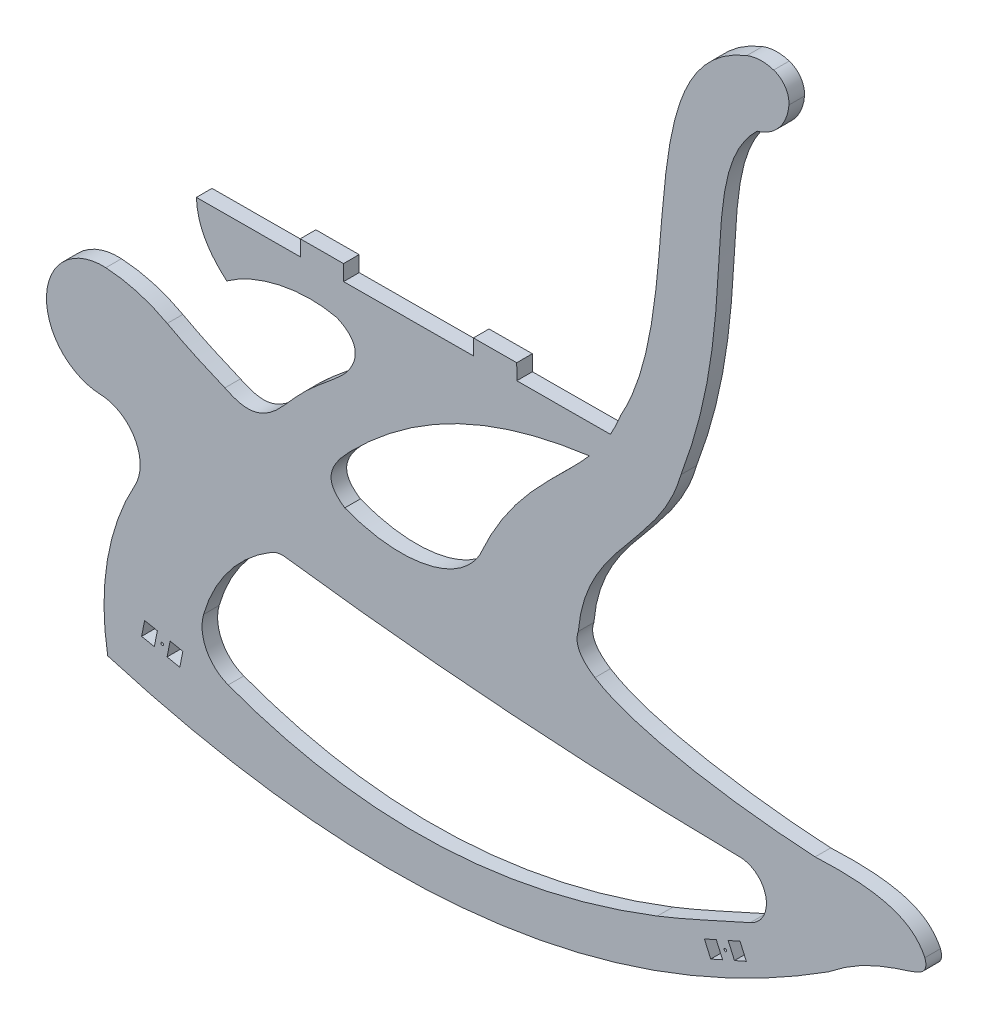
SolidWorks part; units mm, degrees
material "Teak"
ref_plane "Front Plane" through (0, 0, 0) normal (0, 0, 1) x (1, 0, 0)
ref_plane "Top Plane" through (0, 0, 0) normal (0, 1, 0) x (1, 0, 0)
ref_plane "Right Plane" through (0, 0, 0) normal (1, 0, 0) x (0, 0, -1)
sketch "Несущая боковая" plane through (0, 0, 0) normal (0, 0, 1) x (1, 0, 0)
  line L6 (398.785, -200.6515) -> (-79.2948, -202.7)
  arc A0 (568.0858, 187.1743) -> (604.9253, 231.748) centre (555.0835, 235.431) ccw
  arc A1 (604.9253, 231.748) -> (587.3016, 257.9076) centre (579.4885, 233.6276) ccw
  arc A2 (587.3016, 257.9076) -> (556.344, 256.9224) centre (573.2016, 214.0906) ccw
  arc A4 (-150.2921, -526.2545) -> (-190.0816, -455.2016) centre (-192.0175, -502.9531) ccw
  arc A7 (-150.2921, -526.2545) -> (-181.6944, -712.4375) centre (95.3308, -663.4217) ccw
  arc A8 (-183.8786, -325.353) -> (-190.0816, -455.2016) centre (-187.4487, -390.2549) ccw
  arc A9 (-112.9747, -345.6094) -> (-183.8786, -325.353) centre (-193.0224, -491.581) ccw
  arc A10 (560.3467, -608.2215) -> (548.1989, -548.57) centre (547.8281, -579.7082) ccw
  arc A11 (23.5507, -511.1423) -> (548.1989, -548.57) centre (601.0308, 3887.8918) ccw
  arc A12 (7.2112, -514.4863) -> (-70.9864, -615.6156) centre (95.3308, -663.4217) ccw
  arc A13 (-70.9864, -615.6156) -> (-42.6063, -671.9817) centre (-26.3207, -628.4543) ccw
  arc A14 (23.5507, -511.1423) -> (7.2112, -514.4863) centre (20.2245, -536.4807) ccw
  spline S0 degree 3 poles (556.344, 256.9224) (413.4931, 200.7) (492.8039, -30.4464) (410.7267, -175.5993) knots 0.000401 0.000401 0.000401 0.000401 0.043478 0.043478 0.043478 0.043478
  spline S1 degree 3 poles (410.7267, -175.5993) (407.231, -184.6492) (403.2193, -192.9282) (398.785, -200.6515) knots 0.043478 0.043478 0.043478 0.043478 0.086957 0.086957 0.086957 0.086957
  spline S2 degree 3 poles (-79.2948, -202.7) (-78.5172, -227.7) (-66.7741, -249.7094) (-44.1772, -268.7587) knots 0.130435 0.130435 0.130435 0.130435 0.173913 0.173913 0.173913 0.173913
  spline S3 degree 3 poles (-44.1772, -268.7587) (-12.7058, -245.829) (38.9597, -231.7344) (82.6666, -241.804) knots 0.173913 0.173913 0.173913 0.173913 0.217391 0.217391 0.217391 0.217391
  spline S4 degree 3 poles (82.6666, -241.804) (105.6787, -251.6525) (111.2464, -268.6919) (94.2115, -290.7234) knots 0.217391 0.217391 0.217391 0.217391 0.26087 0.26087 0.26087 0.26087
  spline S5 degree 3 poles (94.2115, -290.7234) (87.1581, -299.8457) (74.9831, -308.4217) (61.0599, -320.5021) knots 0.26087 0.26087 0.26087 0.26087 0.304348 0.304348 0.304348 0.304348
  spline S6 degree 3 poles (61.0599, -320.5021) (47.3806, -331.8412) (34.8832, -345.2678) (22.8705, -359.1067) knots 0.304348 0.304348 0.304348 0.304348 0.347826 0.347826 0.347826 0.347826
  spline S7 degree 3 poles (22.8705, -359.1067) (-5.5844, -391.8897) (-25.5922, -386.6363) (-46.4172, -376.7876) knots 0.347826 0.347826 0.347826 0.347826 0.391304 0.391304 0.391304 0.391304
  spline S8 degree 3 poles (-46.4172, -376.7876) (-71.9902, -366.2219) (-92.784, -356.6815) (-112.9747, -345.6094) knots 0.391304 0.391304 0.391304 0.391304 0.434783 0.434783 0.434783 0.434783
  spline S14 degree 3 poles (-181.6944, -712.4375) (138.4622, -807.7317) (410.6911, -765.399) (650.1904, -612.5982) knots 0.652174 0.652174 0.652174 0.652174 0.695652 0.695652 0.695652 0.695652
  spline S15 degree 3 poles (650.1904, -612.5982) (721.7263, -555.1366) (771.3742, -572.8028) (761.971, -542.4383) knots 0.695652 0.695652 0.695652 0.695652 0.73913 0.73913 0.73913 0.73913
  spline S16 degree 3 poles (761.971, -542.4383) (749.9881, -518.2511) (723.1034, -500.8362) (635.2399, -505.0064) knots 0.73913 0.73913 0.73913 0.73913 0.782609 0.782609 0.782609 0.782609
  spline S17 degree 3 poles (635.2399, -505.0064) (572.992, -501.9328) (433.5503, -486.7788) (380.9104, -452.9037) knots 0.782609 0.782609 0.782609 0.782609 0.826087 0.826087 0.826087 0.826087
  spline S18 degree 3 poles (380.9104, -452.9037) (364.7659, -442.5143) (356.7862, -430.3638) (361.7026, -416.2609) knots 0.826087 0.826087 0.826087 0.826087 0.869565 0.869565 0.869565 0.869565
  spline S19 degree 3 poles (361.7026, -416.2609) (369.7577, -319.5618) (455.7474, -287.137) (480.2427, -200.3025) knots 0.869565 0.869565 0.869565 0.869565 0.913043 0.913043 0.913043 0.913043
  spline S20 degree 3 poles (480.2427, -200.3025) (553.5443, -5.6015) (495.01, 115.2768) (568.0858, 187.1743) knots 0.913043 0.913043 0.913043 0.913043 0.956522 0.956522 0.956522 0.956522
  spline S25 degree 3 poles (452.9574, -655.3702) (274.7112, -724.495) (109.7393, -728.981) (-42.6063, -671.9817) knots 0.555556 0.555556 0.555556 0.555556 0.666667 0.666667 0.666667 0.666667
  spline S26 degree 3 poles (560.3467, -608.2215) (524.5503, -623.9377) (490.7002, -640.4881) (452.9574, -655.3702) knots 0.444444 0.444444 0.444444 0.444444 0.555556 0.555556 0.555556 0.555556
  spline S31 degree 3 poles (97.4618, -368.9486) (168.6207, -296.3511) (255.442, -250.0892) (374.5085, -234.3308) knots 0.75 0.75 0.75 0.75 1 1 1 1
  spline S32 degree 3 poles (92.0908, -427.5464) (69.7947, -412.5311) (70.4905, -396.4567) (97.4618, -368.9486) knots 0.5 0.5 0.5 0.5 0.75 0.75 0.75 0.75
  spline S33 degree 3 poles (247.8827, -396.6458) (222.4754, -441.0979) (152.6914, -451.7196) (92.0908, -427.5464) knots 0.25 0.25 0.25 0.25 0.5 0.5 0.5 0.5
  spline S34 degree 3 poles (374.5085, -234.3308) (336.7044, -278.0035) (285.6362, -310.9643) (247.8827, -396.6458) knots 0 0 0 0 0.25 0.25 0.25 0.25
  dimension "D2" = 65
sketch "Боковая под поперечины" plane through (0, 0, 0) normal (0, 0, 1) x (1, 0, 0)
  line L15 (-159.6049, -346.9107) -> (-207.6507, -344.8161) construction
  line L16 (-207.6507, -344.8161) -> (-235.0021, -434.5683)
  line L56 (-207.6507, -344.8161) -> (-159.6963, -346.9068)
  line L57 (-159.6963, -346.9068) -> (-148.2015, -350.3521)
  line L58 (-148.2015, -350.3521) -> (-104.2437, -369.6319)
  line L59 (-104.2437, -369.6319) -> (-95.353, -374.2095)
  line L60 (-95.353, -374.2095) -> (-51.5894, -393.9261)
  line L61 (-51.5894, -393.9261) -> (-42.3459, -397.7417)
  line L62 (-42.3459, -397.7417) -> (2.1537, -415.7357)
  line L63 (2.1537, -415.7357) -> (11.4455, -419.432)
  line L64 (11.4455, -419.432) -> (56.3986, -436.2612)
  line L65 (56.3986, -436.2612) -> (65.8381, -439.5619)
  line L66 (65.8381, -439.5619) -> (111.7403, -453.5971)
  line L67 (111.7403, -453.5971) -> (121.3499, -456.3643)
  line L68 (121.3499, -456.3643) -> (169.2689, -459.1514)
  line L69 (169.2689, -459.1514) -> (179.2066, -458.0374)
  line L70 (179.2066, -458.0374) -> (224.5179, -442.198)
  line L71 (224.5179, -442.198) -> (232.8956, -436.7378)
  line L72 (232.8956, -436.7378) -> (261.7321, -398.3651)
  line L73 (261.7321, -398.3651) -> (267.2053, -389.9959)
  line L74 (267.2053, -389.9959) -> (294.9373, -350.8177)
  line L75 (294.9373, -350.8177) -> (300.8954, -342.7864)
  line L76 (300.8954, -342.7864) -> (330.585, -305.0699)
  line L77 (330.585, -305.0699) -> (336.9867, -297.3877)
  line L78 (336.9867, -297.3877) -> (368.9263, -261.5566)
  line L79 (368.9263, -261.5566) -> (376.1332, -254.6241)
  line L80 (376.1332, -254.6241) -> (406.9239, -217.801)
  line L81 (406.9239, -217.801) -> (412.4436, -209.4624)
  line L82 (412.4436, -209.4624) -> (434.4129, -166.7851)
  line L83 (438.0837, -157.4832) -> (452.6073, -111.7332)
  line L84 (452.6073, -111.7332) -> (454.9033, -102.0003)
  line L85 (454.9033, -102.0003) -> (464.25, -54.9191)
  line L86 (464.25, -54.9191) -> (465.6878, -45.023)
  line L87 (465.6878, -45.023) -> (472.014, 2.5582)
  line L88 (472.014, 2.5582) -> (473.0512, 12.5043)
  line L89 (473.0512, 12.5043) -> (478.3742, 60.2082)
  line L90 (478.3742, 60.2082) -> (479.4656, 70.1485)
  line L91 (479.4656, 70.1485) -> (486.2184, 117.6711)
  line L92 (486.2184, 117.6711) -> (487.9962, 127.5118)
  line L93 (487.9962, 127.5118) -> (500.2801, 173.9134)
  line L94 (500.2801, 173.9134) -> (504.8877, 188.1882)
  line L95 (504.8877, 188.1882) -> (532.6089, 227.3741)
  line L96 (532.6089, 227.3741) -> (546.1164, 235.9502)
  line L97 (546.1164, 235.9502) -> (589.1375, 257.2382)
  line L99 (434.4129, -166.7851) -> (438.0837, -157.4832)
  arc A4 (568.0858, 187.1743) -> (604.9253, 231.748) centre (554.9668, 235.5274) ccw
  arc A7 (604.9253, 231.748) -> (589.1375, 257.2382) centre (579.4223, 233.5866) ccw
  arc A10 (604.9253, 231.748) -> (587.3016, 257.9076) centre (579.4885, 233.6276) ccw construction
  arc A11 (-144.8294, -495.3868) -> (-22.9392, -537.0926) centre (-72.7974, -483.8369) ccw
  arc A12 (7.2112, -514.4863) -> (-22.9392, -537.0926) centre (95.3308, -663.4217) ccw
  arc A13 (23.5507, -511.1423) -> (7.2112, -514.4863) centre (20.2245, -536.4807) ccw
  arc A15 (-144.8294, -495.3868) -> (-190.0816, -455.2016) centre (-192.0175, -502.9531) ccw
  arc A16 (23.5507, -511.1423) -> (352.014, -541.8909) centre (601.0308, 3887.8918) ccw
  arc A17 (-150.2921, -526.2545) -> (-190.0816, -455.2016) centre (-192.0175, -502.9531) ccw construction
  arc A18 (-183.8786, -325.353) -> (-190.0816, -455.2016) centre (-187.4487, -390.2549) ccw construction
  arc A19 (-235.0021, -434.5683) -> (-190.0816, -455.2016) centre (-187.4487, -390.2549) ccw
  arc A20 (23.5507, -511.1423) -> (548.1989, -548.57) centre (601.0308, 3887.8918) ccw construction
  arc A21 (23.5507, -511.1423) -> (7.2112, -514.4863) centre (20.2245, -536.4807) ccw construction
  arc A22 (7.2112, -514.4863) -> (-70.9864, -615.6156) centre (95.3308, -663.4217) ccw construction
  arc A23 (352.014, -541.8909) -> (380.9104, -452.9037) centre (354.7294, -493.5874) ccw
  spline S13 degree 3 poles (380.9104, -452.9037) (364.7659, -442.5143) (356.7861, -430.3638) (361.7026, -416.2609) knots 0.5 0.5 0.5 0.5 0.533333 0.533333 0.533333 0.533333
  spline S14 degree 3 poles (361.7026, -416.2609) (369.7577, -319.5618) (455.7474, -287.137) (480.2427, -200.3025) knots 0.533333 0.533333 0.533333 0.533333 0.566667 0.566667 0.566667 0.566667
  spline S15 degree 3 poles (480.2427, -200.3025) (553.5444, -5.6014) (495.0101, 115.2768) (568.0858, 187.1743) knots 0.566667 0.566667 0.566667 0.566667 0.6 0.6 0.6 0.6
  point P66 (608.2751, 264.1653)
  point P67 (553.7309, 240.2756)
  point P74 (-221.3236, -344.22)
  dimension "D1" = 48
  dimension "D2" = 12
  dimension "D3" = 10
  dimension "D10" = 16
  dimension "D11" = 15
extrude "Несущая" add sketch "Несущая боковая" along normal blind 18
extrude "Боковая" [suppressed] add sketch "Боковая под поперечины" along normal blind 18
sketch "Sketch3" [suppressed] plane through (0, 0, 0) normal (0, 0, 1) x (1, 0, 0)
  line L0 (546.1164, 235.9502) -> (589.1375, 257.2382) construction
  line L2 (-212.8786, -423.719) -> (-206.4654, -402.6745)
  line L3 (-230.0968, -418.4719) -> (-223.6836, -397.4273)
  line L6 (-230.0968, -418.4719) -> (-212.8786, -423.719)
  line L10 (-207.6507, -344.8161) -> (-194.6631, -345.3823) construction
  line L11 (-207.6507, -344.8161) -> (-208.4348, -362.799) construction
  line L12 (-159.6963, -346.9068) -> (-160.4803, -364.8897) construction
  line L13 (-208.4348, -362.799) -> (-195.4471, -363.3652) construction
  line L14 (-194.6631, -345.3823) -> (-195.4471, -363.3652)
  line L15 (-172.684, -346.3405) -> (-173.468, -364.3234)
  line L16 (-173.468, -364.3234) -> (-160.4803, -364.8897) construction
  line L17 (-195.4471, -363.3652) -> (-173.468, -364.3234)
  line L18 (-172.684, -346.3405) -> (-159.6963, -346.9068) construction
  line L19 (-194.6631, -345.3823) -> (-172.684, -346.3405)
  line L37 (-136.2963, -355.5737) -> (-143.5262, -372.0579)
  line L38 (-116.149, -364.4103) -> (-123.3789, -380.8944)
  line L40 (-155.4315, -366.8363) -> (-143.5262, -372.0579) construction
  line L41 (-116.149, -364.4103) -> (-104.2437, -369.6319) construction
  line L42 (-143.5262, -372.0579) -> (-123.3789, -380.8944)
  line L43 (-104.2437, -369.6319) -> (-111.4736, -386.1161) construction
  line L44 (-123.3789, -380.8944) -> (-111.4736, -386.1161) construction
  line L45 (-148.2015, -350.3521) -> (-136.2963, -355.5737) construction
  line L46 (-136.2963, -355.5737) -> (-116.149, -364.4103)
  line L47 (-148.2015, -350.3521) -> (-155.4315, -366.8363) construction
  line L48 (-104.2437, -369.6319) -> (-148.2015, -350.3521) construction
  line L49 (-63.442, -388.5862) -> (-70.8357, -404.9976)
  line L50 (-83.5003, -379.5494) -> (-63.442, -388.5862)
  line L51 (-83.5003, -379.5494) -> (-90.8941, -395.9608)
  line L52 (-63.442, -388.5862) -> (-51.5894, -393.9261) construction
  line L53 (-102.7467, -390.6208) -> (-90.8941, -395.9608) construction
  line L54 (-51.5894, -393.9261) -> (-58.9831, -410.3375) construction
  line L55 (-95.353, -374.2095) -> (-83.5003, -379.5494) construction
  line L56 (-90.8941, -395.9608) -> (-70.8357, -404.9976)
  line L57 (-70.8357, -404.9976) -> (-58.9831, -410.3375) construction
  line L58 (-95.353, -374.2095) -> (-102.7467, -390.6208) construction
  line L59 (-37.0417, -419.3024) -> (-16.646, -427.5497)
  line L60 (-30.2939, -402.615) -> (-9.8983, -410.8623)
  line L61 (-42.3459, -397.7417) -> (-30.2939, -402.615) construction
  line L62 (-9.8983, -410.8623) -> (2.1537, -415.7357) construction
  line L63 (-49.0936, -414.429) -> (-37.0417, -419.3024) construction
  line L64 (-9.8983, -410.8623) -> (-16.646, -427.5497)
  line L65 (-42.3459, -397.7417) -> (-49.0936, -414.429) construction
  line L66 (-16.646, -427.5497) -> (-4.594, -432.423) construction
  line L67 (-30.2939, -402.615) -> (-37.0417, -419.3024)
  line L68 (2.1537, -415.7357) -> (-4.594, -432.423) construction
  line L69 (44.2238, -431.7033) -> (37.9128, -448.5607)
  line L70 (56.3986, -436.2612) -> (50.0876, -453.1186) construction
  line L71 (23.6203, -423.9899) -> (44.2238, -431.7033)
  line L72 (23.6203, -423.9899) -> (17.3094, -440.8473)
  line L73 (5.1346, -436.2894) -> (17.3094, -440.8473) construction
  line L74 (11.4455, -419.432) -> (23.6203, -423.9899) construction
  line L75 (44.2238, -431.7033) -> (56.3986, -436.2612) construction
  line L76 (11.4455, -419.432) -> (5.1346, -436.2894) construction
  line L77 (37.9128, -448.5607) -> (50.0876, -453.1186) construction
  line L78 (17.3094, -440.8473) -> (37.9128, -448.5607)
  line L79 (94.0453, -467.0093) -> (106.4771, -470.8105) construction
  line L80 (65.8381, -439.5619) -> (60.5749, -456.7753) construction
  line L81 (99.3085, -449.7959) -> (94.0453, -467.0093)
  line L82 (78.27, -443.3631) -> (73.0068, -460.5765)
  line L83 (65.8381, -439.5619) -> (78.27, -443.3631) construction
  line L84 (60.5749, -456.7753) -> (73.0068, -460.5765) construction
  line L85 (99.3085, -449.7959) -> (111.7403, -453.5971) construction
  line L86 (111.7403, -453.5971) -> (106.4771, -470.8105) construction
  line L87 (73.0068, -460.5765) -> (94.0453, -467.0093)
  line L88 (78.27, -443.3631) -> (99.3085, -449.7959)
  line L89 (120.3047, -474.3339) -> (133.2828, -475.0888) construction
  line L90 (156.2908, -458.3965) -> (169.2689, -459.1514) construction
  line L91 (133.2828, -475.0888) -> (155.2457, -476.3662)
  line L92 (156.2908, -458.3965) -> (155.2457, -476.3662)
  line L93 (155.2457, -476.3662) -> (168.2237, -477.121) construction
  line L94 (121.3499, -456.3643) -> (134.3279, -457.1191) construction
  line L95 (134.3279, -457.1191) -> (156.2908, -458.3965)
  line L96 (121.3499, -456.3643) -> (120.3047, -474.3339) construction
  line L97 (134.3279, -457.1191) -> (133.2828, -475.0888)
  line L98 (169.2689, -459.1514) -> (168.2237, -477.121) construction
  line L99 (218.1859, -463.4795) -> (230.4577, -459.1897) construction
  line L100 (191.4784, -453.7475) -> (212.2461, -446.4878)
  line L101 (191.4784, -453.7475) -> (197.4182, -470.7393)
  line L102 (185.1464, -475.0291) -> (197.4182, -470.7393) construction
  line L103 (224.5179, -442.198) -> (230.4577, -459.1897) construction
  line L104 (197.4182, -470.7393) -> (218.1859, -463.4795)
  line L105 (179.2066, -458.0374) -> (185.1464, -475.0291) construction
  line L106 (212.2461, -446.4878) -> (224.5179, -442.198) construction
  line L107 (179.2066, -458.0374) -> (191.4784, -453.7475) construction
  line L108 (212.2461, -446.4878) -> (218.1859, -463.4795)
  line L109 (255.0952, -437.1589) -> (268.312, -419.5714)
  line L110 (268.312, -419.5714) -> (276.1219, -409.1788) construction
  line L111 (247.2854, -447.5514) -> (255.0952, -437.1589) construction
  line L112 (240.7055, -426.3452) -> (255.0952, -437.1589)
  line L113 (253.9222, -408.7577) -> (261.7321, -398.3651) construction
  line L114 (261.7321, -398.3651) -> (276.1219, -409.1788) construction
  line L115 (232.8956, -436.7378) -> (240.7055, -426.3452) construction
  line L116 (240.7055, -426.3452) -> (253.9222, -408.7577)
  line L117 (232.8956, -436.7378) -> (247.2854, -447.5514) construction
  line L118 (253.9222, -408.7577) -> (268.312, -419.5714)
  line L119 (267.2053, -389.9959) -> (274.7161, -379.3851) construction
  line L120 (267.2053, -389.9959) -> (281.8971, -400.3954) construction
  line L121 (281.8971, -400.3954) -> (289.4079, -389.7846) construction
  line L122 (274.7161, -379.3851) -> (289.4079, -389.7846)
  line L123 (289.4079, -389.7846) -> (302.1184, -371.828)
  line L124 (287.4266, -361.4284) -> (302.1184, -371.828)
  line L125 (294.9373, -350.8177) -> (309.6292, -361.2172) construction
  line L126 (302.1184, -371.828) -> (309.6292, -361.2172) construction
  line L127 (287.4266, -361.4284) -> (294.9373, -350.8177) construction
  line L128 (274.7161, -379.3851) -> (287.4266, -361.4284)
  line L129 (336.6877, -326.4184) -> (344.7286, -316.2035) construction
  line L130 (323.08, -343.7051) -> (336.6877, -326.4184)
  line L131 (308.9363, -332.5715) -> (322.5441, -315.2848)
  line L132 (300.8954, -342.7864) -> (308.9363, -332.5715) construction
  line L133 (300.8954, -342.7864) -> (315.0391, -353.92) construction
  line L134 (308.9363, -332.5715) -> (323.08, -343.7051)
  line L135 (322.5441, -315.2848) -> (336.6877, -326.4184)
  line L136 (315.0391, -353.92) -> (323.08, -343.7051) construction
  line L137 (330.585, -305.0699) -> (344.7286, -316.2035) construction
  line L138 (322.5441, -315.2848) -> (330.585, -305.0699) construction
  line L139 (336.9867, -297.3877) -> (350.4234, -309.365) construction
  line L140 (360.276, -271.2609) -> (373.7127, -283.2382)
  line L141 (373.7127, -283.2382) -> (382.363, -273.534) construction
  line L142 (350.4234, -309.365) -> (359.0737, -299.6608) construction
  line L143 (359.0737, -299.6608) -> (373.7127, -283.2382)
  line L144 (336.9867, -297.3877) -> (345.637, -287.6834) construction
  line L145 (368.9263, -261.5566) -> (382.363, -273.534) construction
  line L146 (360.276, -271.2609) -> (368.9263, -261.5566) construction
  line L147 (345.637, -287.6834) -> (360.276, -271.2609)
  line L148 (345.637, -287.6834) -> (359.0737, -299.6608)
  line L149 (412.3934, -239.3204) -> (420.7325, -229.3475) construction
  line L150 (398.5847, -227.7739) -> (412.3934, -239.3204)
  line L151 (398.281, -256.1976) -> (412.3934, -239.3204)
  line L152 (389.9419, -266.1706) -> (398.281, -256.1976) construction
  line L153 (406.9239, -217.801) -> (420.7325, -229.3475) construction
  line L154 (376.1332, -254.6241) -> (384.4724, -244.6512) construction
  line L155 (376.1332, -254.6241) -> (389.9419, -266.1706) construction
  line L156 (398.5847, -227.7739) -> (406.9239, -217.801) construction
  line L157 (384.4724, -244.6512) -> (398.281, -256.1976)
  line L158 (384.4724, -244.6512) -> (398.5847, -227.7739)
  line L159 (444.4669, -186.5821) -> (450.4169, -175.0237) construction
  line L160 (428.4629, -178.3436) -> (434.4129, -166.7851) construction
  line L161 (428.4629, -178.3436) -> (444.4669, -186.5821)
  line L162 (418.3936, -197.904) -> (434.3976, -206.1425)
  line L163 (434.3976, -206.1425) -> (444.4669, -186.5821)
  line L164 (412.4436, -209.4624) -> (428.4475, -217.7009) construction
  line L165 (428.4475, -217.7009) -> (434.3976, -206.1425) construction
  line L166 (434.4129, -166.7851) -> (450.4169, -175.0237) construction
  line L167 (418.3936, -197.904) -> (428.4629, -178.3436)
  line L168 (412.4436, -209.4624) -> (418.3936, -197.904) construction
  line L169 (455.24, -162.9296) -> (459.1734, -150.5389) construction
  line L170 (448.6738, -124.1238) -> (452.6073, -111.7332) construction
  line L171 (442.0172, -145.0926) -> (459.1734, -150.5389)
  line L172 (448.6738, -124.1238) -> (465.8301, -129.5702)
  line L173 (438.0837, -157.4832) -> (442.0172, -145.0926) construction
  line L174 (465.8301, -129.5702) -> (469.7635, -117.1795) construction
  line L175 (442.0172, -145.0926) -> (448.6738, -124.1238)
  line L176 (452.6073, -111.7332) -> (469.7635, -117.1795) construction
  line L177 (438.0837, -157.4832) -> (455.24, -162.9296) construction
  line L178 (459.1734, -150.5389) -> (465.8301, -129.5702)
  line L179 (-51.5894, -393.9261) -> (-95.353, -374.2095) construction
  line L180 (2.1537, -415.7357) -> (-42.3459, -397.7417) construction
  line L181 (56.3986, -436.2612) -> (11.4455, -419.432) construction
  line L182 (368.9263, -261.5566) -> (336.9867, -297.3877) construction
  line L183 (406.9239, -217.801) -> (376.1332, -254.6241) construction
  line L184 (434.4129, -166.7851) -> (412.4436, -209.4624) construction
  line L185 (452.6073, -111.7332) -> (438.0837, -157.4832) construction
  line L186 (472.5587, -105.5054) -> (475.0901, -92.7542) construction
  line L187 (457.4347, -89.2492) -> (461.7186, -67.6703)
  line L188 (454.9033, -102.0003) -> (457.4347, -89.2492) construction
  line L189 (457.4347, -89.2492) -> (475.0901, -92.7542)
  line L190 (461.7186, -67.6703) -> (464.25, -54.9191) construction
  line L191 (454.9033, -102.0003) -> (472.5587, -105.5054) construction
  line L192 (464.25, -54.9191) -> (481.9054, -58.4242) construction
  line L193 (475.0901, -92.7542) -> (479.374, -71.1753)
  line L194 (461.7186, -67.6703) -> (479.374, -71.1753)
  line L195 (479.374, -71.1753) -> (481.9054, -58.4242) construction
  line L196 (467.4011, -32.1364) -> (470.3006, -10.3284)
  line L197 (465.6878, -45.023) -> (467.4011, -32.1364) construction
  line L198 (472.014, 2.5582) -> (489.857, 0.1859) construction
  line L199 (485.2441, -34.5088) -> (488.1436, -12.7007)
  line L200 (470.3006, -10.3284) -> (472.014, 2.5582) construction
  line L201 (488.1436, -12.7007) -> (489.857, 0.1859) construction
  line L202 (465.6878, -45.023) -> (483.5308, -47.3954) construction
  line L203 (467.4011, -32.1364) -> (485.2441, -34.5088)
  line L204 (470.3006, -10.3284) -> (488.1436, -12.7007)
  line L205 (483.5308, -47.3954) -> (485.2441, -34.5088) construction
  line L206 (473.0512, 12.5043) -> (474.4928, 25.4241) construction
  line L207 (474.4928, 25.4241) -> (476.9325, 47.2884)
  line L208 (473.0512, 12.5043) -> (490.9401, 10.5082) construction
  line L209 (494.8215, 45.2923) -> (496.2632, 58.2121) construction
  line L210 (476.9325, 47.2884) -> (494.8215, 45.2923)
  line L211 (474.4928, 25.4241) -> (492.3818, 23.428)
  line L212 (490.9401, 10.5082) -> (492.3818, 23.428) construction
  line L213 (492.3818, 23.428) -> (494.8215, 45.2923)
  line L214 (478.3742, 60.2082) -> (496.2632, 58.2121) construction
  line L215 (476.9325, 47.2884) -> (478.3742, 60.2082) construction
  line L216 (486.2184, 117.6711) -> (504.0394, 115.1388) construction
  line L217 (481.2945, 83.0192) -> (484.3895, 104.8004)
  line L218 (499.1154, 80.4869) -> (502.2105, 102.2681)
  line L219 (502.2105, 102.2681) -> (504.0394, 115.1388) construction
  line L220 (484.3895, 104.8004) -> (486.2184, 117.6711) construction
  line L221 (484.3895, 104.8004) -> (502.2105, 102.2681)
  line L222 (479.4656, 70.1485) -> (481.2945, 83.0192) construction
  line L223 (479.4656, 70.1485) -> (497.2865, 67.6162) construction
  line L224 (481.2945, 83.0192) -> (499.1154, 80.4869)
  line L225 (497.2865, 67.6162) -> (499.1154, 80.4869) construction
  line L226 (500.2801, 173.9134) -> (517.6807, 169.307) construction
  line L227 (505.3968, 122.9054) -> (508.7237, 135.4725) construction
  line L228 (491.3231, 140.0789) -> (496.9532, 161.3463)
  line L229 (514.3538, 156.7399) -> (517.6807, 169.307) construction
  line L230 (487.9962, 127.5118) -> (491.3231, 140.0789) construction
  line L231 (487.9962, 127.5118) -> (505.3968, 122.9054) construction
  line L232 (491.3231, 140.0789) -> (508.7237, 135.4725)
  line L233 (496.9532, 161.3463) -> (514.3538, 156.7399)
  line L234 (508.7237, 135.4725) -> (514.3538, 156.7399)
  line L235 (496.9532, 161.3463) -> (500.2801, 173.9134) construction
  line L236 (512.3955, 198.8011) -> (525.1011, 216.7613)
  line L237 (504.8877, 188.1882) -> (519.5824, 177.7928) construction
  line L238 (525.1011, 216.7613) -> (532.6089, 227.3741) construction
  line L239 (512.3955, 198.8011) -> (527.0902, 188.4056)
  line L240 (525.1011, 216.7613) -> (539.7958, 206.3658)
  line L241 (532.6089, 227.3741) -> (547.3036, 216.9787) construction
  line L242 (504.8877, 188.1882) -> (512.3955, 198.8011) construction
  line L243 (539.7958, 206.3658) -> (547.3036, 216.9787) construction
  line L244 (519.5824, 177.7928) -> (527.0902, 188.4056) construction
  line L245 (527.0902, 188.4056) -> (539.7958, 206.3658)
  line L246 (589.1375, 257.2382) -> (597.1205, 241.1053) construction
  line L247 (557.7679, 241.7157) -> (565.7509, 225.5827)
  line L248 (546.1164, 235.9502) -> (557.7679, 241.7157) construction
  line L249 (577.4859, 251.4727) -> (585.469, 235.3398)
  line L250 (585.469, 235.3398) -> (597.1205, 241.1053) construction
  line L251 (557.7679, 241.7157) -> (577.4859, 251.4727)
  line L252 (546.1164, 235.9502) -> (554.0994, 219.8172) construction
  line L253 (565.7509, 225.5827) -> (585.469, 235.3398)
  line L254 (577.4859, 251.4727) -> (589.1375, 257.2382) construction
  line L255 (554.0994, 219.8172) -> (565.7509, 225.5827) construction
  line L256 (464.25, -54.9191) -> (454.9033, -102.0003) construction
  line L257 (472.014, 2.5582) -> (465.6878, -45.023) construction
  line L258 (486.2184, 117.6711) -> (479.4656, 70.1485) construction
  line L259 (500.2801, 173.9134) -> (487.9962, 127.5118) construction
  line L260 (487.9962, 127.5118) -> (486.2184, 117.6711) construction
  line L261 (532.6089, 227.3741) -> (504.8877, 188.1882) construction
  line L262 (504.8877, 188.1882) -> (500.2801, 173.9134) construction
  line L264 (-223.6836, -397.4273) -> (-206.4654, -402.6745)
  line L269 (-207.6507, -344.8161) -> (-235.0021, -434.5683) construction
  point P1 (-226.8902, -407.9496)
  dimension "D1" = 66
  dimension "D2" = 18
  dimension "D3" = 22
extrude "Шипы" [suppressed] cut sketch "Sketch3" along normal through all
sketch "Sketch4" [suppressed] plane through (0, 0, 18) normal (0, 0, 1) x (1, 0, 0)
  line L0 (-208.4348, -362.799) -> (-221.0097, -388.653) construction
  line L1 (-221.0097, -388.653) -> (-207.6507, -344.8161) construction
  line L2 (-207.6507, -344.8161) -> (-208.4348, -362.799) construction
  line L4 (-217.7838, -439.8154) -> (-237.4507, -429.7729) construction
  line L5 (-237.4507, -429.7729) -> (-240.164, -452.0896) construction
  line L6 (-240.164, -452.0896) -> (-213.0497, -450.0009) construction
  arc A1 (-235.0021, -434.5683) -> (-190.0816, -455.2016) centre (-187.4487, -390.2549) ccw construction
extrude "Излишки" [suppressed] cut sketch "Sketch4" against normal up to next
sketch "Sketch5" plane through (0, 0, 18) normal (0, 0, 1) x (1, 0, 0)
  line L1 (40.627, -184.186) -> (90.6265, -183.9718)
  line L2 (40.627, -184.186) -> (40.7041, -202.1858)
  line L3 (40.7041, -202.1858) -> (90.7037, -201.9716)
  line L4 (90.6265, -183.9718) -> (90.7037, -201.9716)
  line L5 (398.785, -200.6515) -> (-79.2948, -202.7) construction
  line L6 (240.6251, -183.329) -> (290.6247, -183.1148)
  line L7 (240.6251, -183.329) -> (240.7023, -201.3289)
  line L8 (240.7023, -201.3289) -> (290.7018, -201.1146)
  line L9 (290.6247, -183.1148) -> (290.7018, -201.1146)
  dimension "D1" = 18
  dimension "D2" = 150
  dimension "D3" = 120
  dimension "D4" = 50
extrude "Шипы на подлокотниках" add sketch "Sketch5" against normal up to surface (18 mm away) up to face at (168.5307, -593.8353, 0)
sketch "Sketch6" plane through (0, 0, 18) normal (0, 0, 1) x (1, 0, 0)
  line L0 (-139.0626, -655.7461) -> (-142.5889, -673.3973)
  line L1 (-142.5889, -673.3973) -> (-127.8796, -676.3359)
  line L2 (-127.8796, -676.3359) -> (-124.3533, -658.6847)
  line L3 (-124.3533, -658.6847) -> (-139.0626, -655.7461)
  line L4 (-127.8796, -676.3359) -> (-113.1702, -679.2745) construction
  line L5 (-113.1702, -679.2745) -> (-109.6439, -661.6232)
  line L6 (-109.6439, -661.6232) -> (-94.9346, -664.5618)
  line L7 (-94.9346, -664.5618) -> (-98.4609, -682.213)
  line L8 (-98.4609, -682.213) -> (-113.1702, -679.2745)
  line L9 (-120.5249, -677.8052) -> (-116.9986, -660.154) construction
  line L10 (-124.3533, -658.6847) -> (-109.6439, -661.6232) construction
  line L11 (-126.1164, -667.5103) -> (-111.4071, -670.4489) construction
  line L12 (521.0426, -644.9347) -> (534.7498, -638.8426) construction
  line L13 (555.7675, -649.1991) -> (542.0603, -655.2912)
  line L14 (535.2067, -658.3373) -> (527.8962, -641.8886) construction
  line L15 (521.0426, -644.9347) -> (507.3355, -651.0268)
  line L16 (514.646, -667.4754) -> (528.3531, -661.3833)
  line L17 (528.3531, -661.3833) -> (542.0603, -655.2912) construction
  line L18 (528.3531, -661.3833) -> (521.0426, -644.9347)
  line L19 (542.0603, -655.2912) -> (534.7498, -638.8426)
  line L20 (524.6979, -653.159) -> (538.4051, -647.0669) construction
  line L21 (548.457, -632.7505) -> (555.7675, -649.1991)
  line L22 (507.3355, -651.0268) -> (514.646, -667.4754)
  line L23 (534.7498, -638.8426) -> (548.457, -632.7505)
  circle A2 centre (531.5515, -650.113) radius 1.5
  circle A4 centre (-118.7618, -668.9796) radius 1.5
  dimension "D1" = 18
  dimension "D4" = 3
  dimension "D6" = 3
  dimension "D2" = 15
  dimension "D5" = 15
extrude "Под ребра жесткости" cut sketch "Sketch6" against normal up to next
sketch "Sketch7" [suppressed] plane through (0, 0, 18) normal (0, 0, 1) x (1, 0, 0)
  line L0 (567.6269, 246.5942) -> (583.0969, 215.468) construction
  line L1 (577.4859, 251.4727) -> (557.7679, 241.7157) construction
  circle A0 centre (583.0969, 215.468) radius 10 construction
  circle A1 centre (583.0969, 215.468) radius 4
  circle A2 centre (354.7294, -493.5874) radius 4
  circle A3 centre (-72.7974, -483.8369) radius 4
  arc A4 (352.014, -541.8909) -> (380.9104, -452.9037) centre (354.7294, -493.5874) ccw construction
  arc A5 (-144.8294, -495.3868) -> (-22.9392, -537.0926) centre (-72.7974, -483.8369) ccw construction
  dimension "D1" = 8
  dimension "D2" = 20
extrude "Под болты М8" [suppressed] cut sketch "Sketch7" against normal blind 20
sketch "Sketch9" [suppressed] plane through (0, 0, 18) normal (0, 0, 1) x (1, 0, 0)
  circle A1 centre (-150.0179, -416.742) radius 1.5
  circle A2 centre (-19.0866, -469.5934) radius 1.5
  circle A3 centre (116.1327, -506.7832) radius 1.5
  circle A4 centre (265.4187, -506.7832) radius 1.5
  circle A5 centre (335.948, -380.5609) radius 1.5
  circle A6 centre (431.4673, -250.6533) radius 1.5
  circle A7 centre (486.9514, -124.9981) radius 1.5
  circle A8 centre (512.1042, 60.8892) radius 1.5
  dimension "D1" = 3
extrude "Под шурупы" [suppressed] cut sketch "Sketch9" against normal up to next
sketch "Sketch10" [suppressed] plane through (0, 0, 20) normal (0, 0, 1) x (1, 0, 0)
  circle A0 centre (-89.3655, -525.6855) radius 4
  circle A1 centre (349.1273, -502.2927) radius 4
  circle A2 centre (583.0969, 215.468) radius 4
  circle A3 centre (583.0969, 215.468) radius 4 construction
  circle A4 centre (349.1273, -502.2927) radius 4 construction
  circle A5 centre (-89.3655, -525.6855) radius 4 construction
extrude "Под болты М8 в несущей" [suppressed] cut sketch "Sketch10" against normal up to next
equation "\"mm\"=20"
